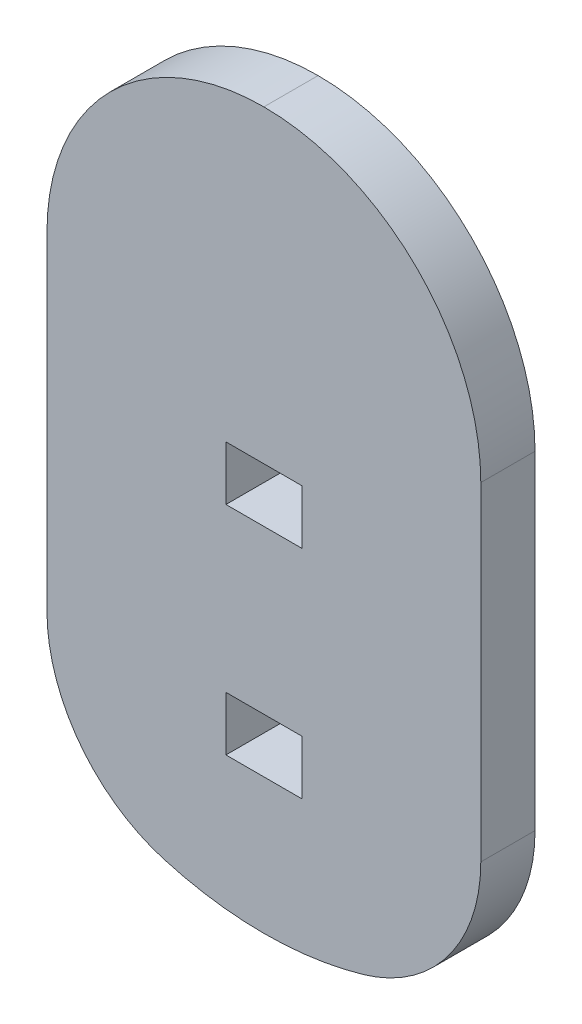
SolidWorks part; units mm, degrees
material "Acrylic (Medium-high impact)"
ref_plane "Front Plane" through (0, 0, 0) normal (0, 0, 1) x (1, 0, 0)
ref_plane "Top Plane" through (0, 0, 0) normal (0, 1, 0) x (1, 0, 0)
ref_plane "Right Plane" through (0, 0, 0) normal (1, 0, 0) x (0, 0, -1)
sketch "Sketch1" plane through (0, 0, 0) normal (0, 0, 1) x (1, 0, 0)
  circle A0 centre (0, 0) radius 33
  point P0 (0, 0)
  dimension "D1" = 66
extrude "Boss-Extrude1" add sketch "Sketch1" along normal blind 5
sketch "Sketch10" plane through (0, 0, 5) normal (0, 0, 1) x (1, 0, 0)
  line L0 (-20, 26.2488) -> (-20, -26.2488)
  line L1 (20, 26.2488) -> (20, -26.2488)
  circle A0 centre (0, 0) radius 33 construction
  arc A1 (-20, 26.2488) -> (-20, -26.2488) centre (0, 0) ccw
  arc A2 (20, -26.2488) -> (20, 26.2488) centre (0, 0) ccw
  dimension "D1" = 20
  dimension "D2" = 40
extrude "Cut-Extrude3" cut sketch "Sketch10" against normal blind 10
fillet "Fillet2" radius 20 2 edges at (-20, 26.2488, 2.5) (20, 26.2488, 2.5)
fillet "Fillet3" radius 15 2 edges at (20, -26.2488, 2.5) (-20, -26.2488, 2.5)
sketch "Sketch11" plane through (0, 0, 5) normal (0, 0, 1) x (1, 0, 0)
  line L1 (-3.5, 4.5) -> (3.5, 4.5)
  line L2 (-3.5, 4.5) -> (-3.5, -0.5)
  line L3 (-3.5, -0.5) -> (3.5, -0.5)
  line L4 (3.5, 4.5) -> (3.5, -0.5)
  line L5 (-3.5, -15.5) -> (3.5, -15.5)
  line L6 (-3.5, -15.5) -> (-3.5, -20.5)
  line L7 (-3.5, -20.5) -> (3.5, -20.5)
  line L8 (3.5, -15.5) -> (3.5, -20.5)
  point P10 (0, -0.5)
  dimension "D1" = 7
  dimension "D2" = 5
  dimension "D3" = 28.5
  dimension "D4" = 15
extrude "Cut-Extrude4" cut sketch "Sketch11" against normal blind 10
sketch "Sketch4" plane through (0, 0, 5) normal (0, 0, 1) x (1, 0, 0)
  line L1 (-11, 4.5) -> (11, 4.5)
  line L2 (-11, 4.5) -> (-11, -0.5)
  line L3 (-11, -0.5) -> (11, -0.5)
  line L4 (11, 4.5) -> (11, -0.5)
  line L5 (-11, 4.5) -> (11, -0.5) construction
  line L6 (-11, -0.5) -> (11, 4.5) construction
  point P0 (0, 2)
  dimension "D1" = 22
  dimension "D2" = 5
  dimension "D3" = 2
extrude "Boss-Extrude2" [suppressed] add sketch "Sketch4" along normal blind 35
sketch "Sketch5" [suppressed] plane through (0, 4.5, 0) normal (0, 1, 0) x (1, 0, 0)
  line L1 (-6, -11) -> (6, -11)
  line L2 (-6, -11) -> (-6, -34)
  line L3 (-6, -34) -> (6, -34)
  line L4 (6, -11) -> (6, -34)
  line L5 (-6, -11) -> (6, -34) construction
  line L6 (-6, -34) -> (6, -11) construction
  line L7 (-11, -40) -> (-11, -5) construction
  line L8 (11, -40) -> (-11, -40) construction
  point P0 (0, -22.5)
  point P10 (-11, -22.5)
  point P12 (0, -40)
  dimension "D1" = 12
  dimension "D2" = 23
extrude "Cut-Extrude1" [suppressed] cut sketch "Sketch5" against normal blind 5
sketch "Sketch6" [suppressed] plane through (0, 4.5, 0) normal (0, 1, 0) x (1, 0, 0)
  line L0 (0, -8) -> (0, -37) construction
  line L1 (-6, -11) -> (-6, -34) construction
  line L2 (-6, -34) -> (6, -34) construction
  circle A0 centre (0, -8) radius 1.25
  circle A1 centre (0, -37) radius 1.25
  point P4 (0, -22.5)
  point P7 (-6, -22.5)
  point P10 (0, -34)
  dimension "D1" = 2.5
  dimension "D2" = 29
extrude "Cut-Extrude2" [suppressed] cut sketch "Sketch6" against normal blind 5
sketch "Sketch7" [suppressed] plane through (0, 0, 40) normal (0, 0, 1) x (1, 0, 0)
  line L0 (11, -0.5) -> (11, 4.5) construction
  line L1 (-11, 4.5) -> (11, 4.5)
  line L2 (-11, 4.5) -> (-11, -15.5)
  line L3 (-11, -15.5) -> (11, -15.5)
  line L4 (11, 4.5) -> (11, -15.5)
  line L5 (11, -0.5) -> (11, 4.5) construction
  dimension "D1" = 20
extrude "Boss-Extrude3" [suppressed] add sketch "Sketch7" along normal blind 5
sketch "Sketch8" [suppressed] plane through (0, -15.5, 0) normal (0, -1, 0) x (1, 0, 0)
  line L1 (-11, 45) -> (11, 45)
  line L2 (-11, 45) -> (-11, 5)
  line L3 (-11, 5) -> (11, 5)
  line L4 (11, 45) -> (11, 5)
extrude "Boss-Extrude4" [suppressed] add sketch "Sketch8" along normal blind 5
sketch "Sketch9" [suppressed] plane through (0, -20.5, 0) normal (0, -1, 0) x (1, 0, 0)
  line L0 (-11, 5) -> (11, 5) construction
  circle A0 centre (0, 27.5) radius 3.75
  dimension "D1" = 7.5
  dimension "D2" = 22.5
extrude "Boss-Extrude5" [suppressed] add sketch "Sketch9" along normal blind 7
fillet "Fillet4" [suppressed] radius 0.5
